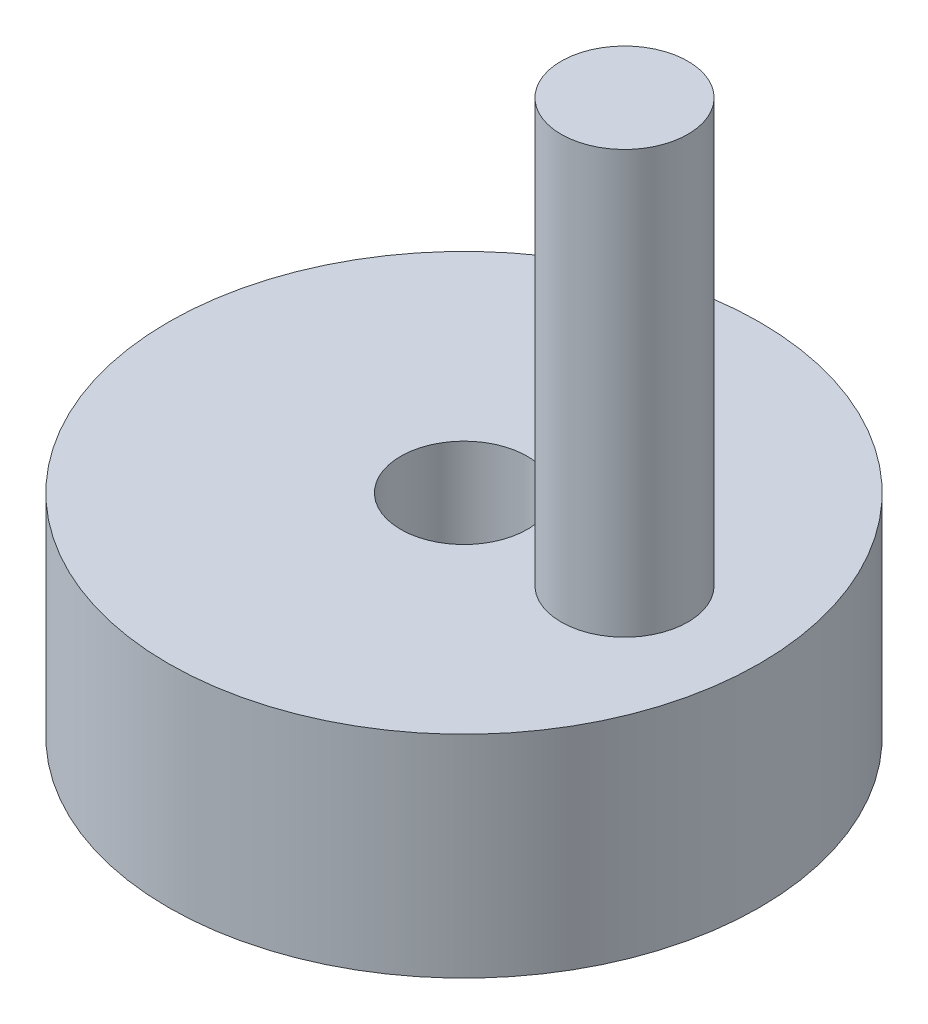
SolidWorks part; units mm, degrees
ref_plane "Front Plane" through (0, 0, 0) normal (0, 0, 1) x (1, 0, 0)
ref_plane "Top Plane" through (0, 0, 0) normal (0, 1, 0) x (1, 0, 0)
ref_plane "Right Plane" through (0, 0, 0) normal (1, 0, 0) x (0, 0, -1)
sketch "Sketch1" plane through (0, 0, 0) normal (0, 1, 0) x (1, 0, 0)
  circle A0 centre (0, 0) radius 70
  circle A2 centre (0, 0) radius 15
  dimension "D1" = 140
  dimension "D2" = 30
extrude "Boss-Extrude1" add sketch "Sketch1" along normal blind 50
sketch "Sketch2" plane through (0, 50, 0) normal (0, 1, 0) x (1, 0, 0)
  line L0 (-55, 0) -> (55, 0) construction
  circle A0 centre (38, 0) radius 15
  dimension "D1" = 30
  dimension "D2" = 38
extrude "Boss-Extrude2" add sketch "Sketch2" along normal blind 100
